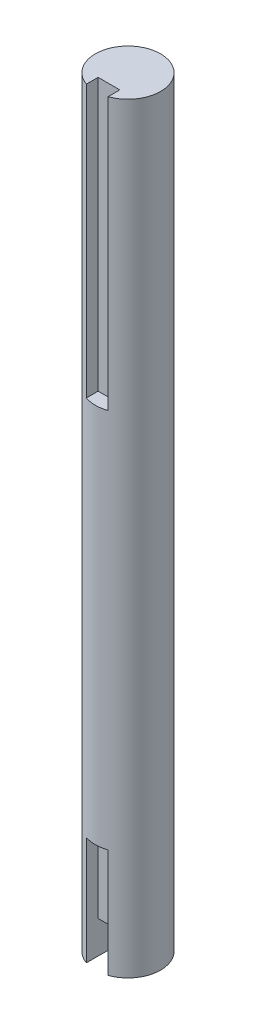
SolidWorks part; units mm, degrees
ref_plane "Front Plane" through (0, 0, 0) normal (0, 0, 1) x (1, 0, 0)
ref_plane "Top Plane" through (0, 0, 0) normal (0, 1, 0) x (1, 0, 0)
ref_plane "Right Plane" through (0, 0, 0) normal (1, 0, 0) x (0, 0, -1)
sketch "Sketch1" plane through (0, 0, 0) normal (0, 1, 0) x (1, 0, 0)
  circle A0 centre (0, 0) radius 6
  dimension "D1" = 12
extrude "Boss-Extrude1" add sketch "Sketch1" along normal blind 104 and the other way blind 36
sketch "Sketch2" plane through (0, 0, 0) normal (0, 1, 0) x (1, 0, 0)
  line L1 (-2, -8.5) -> (2, -8.5)
  line L2 (-2, -8.5) -> (-2, -3.5)
  line L3 (-2, -3.5) -> (2, -3.5)
  line L4 (2, -8.5) -> (2, -3.5)
  line L5 (-2, -8.5) -> (2, -3.5) construction
  line L6 (-2, -3.5) -> (2, -8.5) construction
  circle A0 centre (0, 0) radius 6 construction
  point P0 (0, -6)
  dimension "D1" = 2.5
  dimension "D2" = 4
extrude "Cut-Extrude3" cut sketch "Sketch2" against normal blind 0.0001 and the other way blind 20 from surface starting at face at (0, -36, 6)
extrude "Cut-Extrude4" cut sketch "Sketch2<2>" against normal blind 50 from surface starting at face at (0, 104, 6)
sketch "Sketch2<2>" plane through (0, 0, 0) normal (0, 1, 0) x (1, 0, 0) same geometry as "Sketch2"
sketch "Sketch3" plane through (0, 0, 0) normal (0, 1, 0) x (1, 0, 0)
  line L1 (-2, -11) -> (2, -11)
  line L2 (-2, -11) -> (-2, -1)
  line L3 (-2, -1) -> (2, -1)
  line L4 (2, -11) -> (2, -1)
  line L5 (-2, -11) -> (2, -1) construction
  line L6 (-2, -1) -> (2, -11) construction
  arc A0 (-2, -5.6569) -> (2, -5.6569) centre (0, 0) ccw construction
  point P0 (0, -6)
  dimension "D1" = 4
  dimension "D2" = 5
extrude "Cut-Extrude6" cut sketch "Sketch3" along normal blind 6 from surface starting at face at (0, -36, 1.6642)
sketch "Sketch4" plane through (0, 0, 0) normal (1, 0, 0) x (0, 0, -1)
  line L0 (0.1716, 107.721) -> (0.1716, -45.4994) construction
